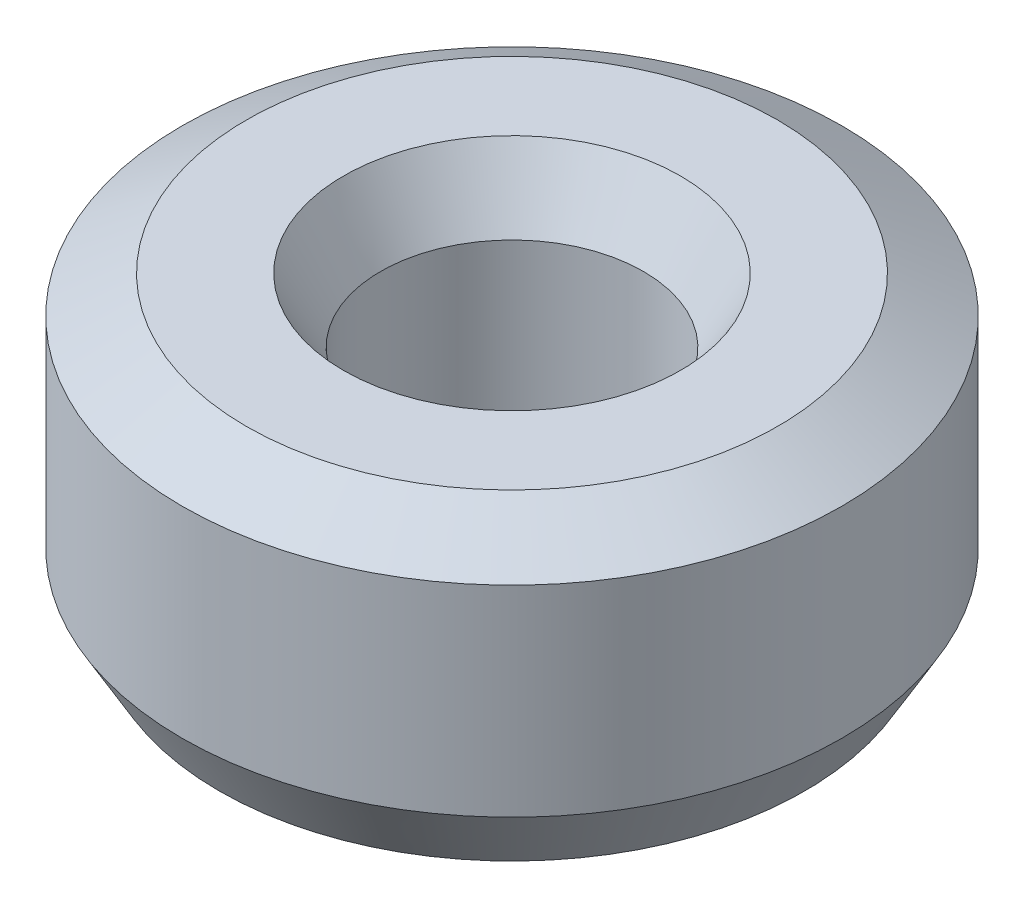
SolidWorks part; units mm, degrees
ref_plane "Front Plane" through (0, 0, 0) normal (0, 0, 1) x (1, 0, 0)
ref_plane "Top Plane" through (0, 0, 0) normal (0, 1, 0) x (1, 0, 0)
ref_plane "Right Plane" through (0, 0, 0) normal (1, 0, 0) x (0, 0, -1)
sketch "Sketch1" plane through (0, 0, 0) normal (0, 1, 0) x (1, 0, 0)
  circle A0 centre (0, 0) radius 35
  dimension "SLEEVE_OD" = 70
extrude "Boss-Extrude1" add sketch "Sketch1" along normal blind 32.08
sketch "Sketch2" plane through (0, 0, 0) normal (0, 1, 0) x (1, 0, 0)
  circle A0 centre (0, 0) radius 13.9549
  dimension "BORE_D" = 27.9097
extrude "Cut-Extrude1" cut sketch "Sketch2" along normal through all
chamfer "Chamfer1" distance 3.9329 angle 60 4 edges at (0, 32.08, 13.9549) (0, 0, 13.9549) (0, 0, 35) (0, 32.08, 35) first distance on face at (0, 32.08, 13.9549) first distance on face at (0, 0, 13.9549) first distance on face at (0, 32.08, 35)
